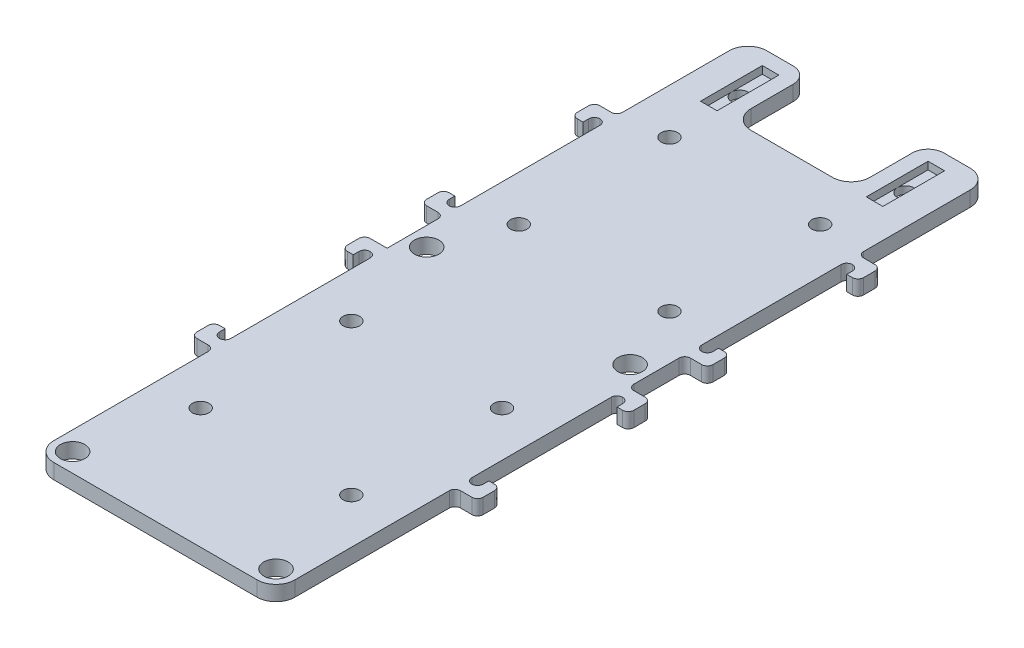
SolidWorks part; units mm, degrees
ref_plane "Front Plane" through (0, 0, 0) normal (0, 0, 1) x (1, 0, 0)
ref_plane "Top Plane" through (0, 0, 0) normal (0, 1, 0) x (1, 0, 0)
ref_plane "Right Plane" through (0, 0, 0) normal (1, 0, 0) x (0, 0, -1)
sketch "Sketch1" plane through (0, 0, 0) normal (0, 1, 0) x (1, 0, 0)
  line L0 (0, 42.225) -> (0, -42.225) construction
  line L1 (16, 42.225) -> (-16, 42.225)
  line L2 (16, 42.225) -> (16, -42.225)
  line L3 (16, -42.225) -> (-16, -42.225)
  line L4 (-16, 42.225) -> (-16, -42.225)
  line L5 (16, 42.225) -> (-16, -42.225) construction
  line L6 (16, -42.225) -> (-16, 42.225) construction
  line L12 (-12.1, 50.425) -> (-12.1, 52.425) construction
  line L17 (-11, 52.425) -> (-11, 42.225) construction
  line L18 (-7.9, 42.225) -> (-14.1, 42.225)
  line L20 (-10, 36) -> (10, 36)
  line L21 (-10, 36) -> (-10, 16)
  line L22 (-10, 16) -> (10, 16)
  line L23 (10, 36) -> (10, 16)
  line L24 (-10, 36) -> (10, 16) construction
  line L25 (-10, 16) -> (10, 36) construction
  line L26 (-14.5, 10.775) -> (14.5, 10.775)
  line L27 (-14.5, 10.775) -> (-14.5, 41.225)
  line L28 (-14.5, 41.225) -> (14.5, 41.225)
  line L29 (14.5, 10.775) -> (14.5, 41.225)
  line L30 (-14.5, 10.775) -> (14.5, 41.225) construction
  line L31 (-14.5, 41.225) -> (14.5, 10.775) construction
  line L32 (-10, -6.225) -> (10, -6.225)
  line L33 (-10, -6.225) -> (-10, -26.225)
  line L34 (-10, -26.225) -> (10, -26.225)
  line L35 (10, -6.225) -> (10, -26.225)
  line L36 (-10, -6.225) -> (10, -26.225) construction
  line L37 (-10, -26.225) -> (10, -6.225) construction
  line L38 (-15.75, -36.225) -> (15.75, -36.225)
  line L39 (-15.75, -36.225) -> (-15.75, 3.775)
  line L40 (-15.75, 3.775) -> (15.75, 3.775)
  line L41 (15.75, -36.225) -> (15.75, 3.775)
  line L42 (-15.75, -36.225) -> (15.75, 3.775) construction
  line L43 (-15.75, 3.775) -> (15.75, -36.225) construction
  line L48 (-7.9, 42.225) -> (-7.9, 52.425)
  line L49 (-7.9, 52.425) -> (-14.1, 52.425)
  line L59 (-14.1, 42.225) -> (-14.1, 52.425)
  line L63 (-12.1, 50.425) -> (-9.9, 50.425)
  line L64 (-12.1, 50.425) -> (-12.1, 42.225)
  line L65 (-12.1, 42.225) -> (-9.9, 42.225)
  line L66 (-9.9, 50.425) -> (-9.9, 42.225)
  line L67 (-12.1, 50.425) -> (-9.9, 42.225) construction
  line L68 (-12.1, 42.225) -> (-9.9, 50.425) construction
  line L69 (-12.1, 50.425) -> (-14.1, 50.425) construction
  line L74 (7.9, 42.225) -> (14.1, 42.225)
  line L75 (14.1, 42.225) -> (14.1, 52.425)
  line L76 (7.9, 52.425) -> (14.1, 52.425)
  line L77 (7.9, 42.225) -> (7.9, 52.425)
  line L78 (12.1, 50.425) -> (9.9, 50.425)
  line L79 (12.1, 50.425) -> (12.1, 42.225)
  line L80 (12.1, 42.225) -> (9.9, 42.225)
  line L81 (9.9, 50.425) -> (9.9, 42.225)
  line L82 (-14.5, 10.775) -> (-14.5, 3.775) construction
  line L83 (-14.5, 7.275) -> (16, 7.275) construction
  line L89 (-13.5, -37.225) -> (-16, -37.225) construction
  line L94 (-14.1, 52.425) -> (-16, 52.425)
  line L95 (-14.1, 52.425) -> (-14.1, 42.225)
  line L96 (-14.1, 42.225) -> (-16, 42.225)
  line L97 (-16, 52.425) -> (-16, 42.225)
  line L98 (14.1, 52.425) -> (16, 52.425)
  line L99 (14.1, 52.425) -> (14.1, 42.225)
  line L100 (14.1, 42.225) -> (16, 42.225)
  line L101 (16, 52.425) -> (16, 42.225)
  circle A3 centre (-10, 36) radius 1.1
  circle A4 centre (10, 36) radius 1.1
  circle A5 centre (10, 16) radius 1.1
  circle A6 centre (-10, 16) radius 1.1
  circle A7 centre (-10, -6.225) radius 1.1
  circle A8 centre (10, -6.225) radius 1.1
  circle A9 centre (10, -26.225) radius 1.1
  circle A10 centre (-10, -26.225) radius 1.1
  circle A37 centre (-13.5, 7.275) radius 2.5
  circle A38 centre (-13.5, 7.275) radius 1.625
  circle A39 centre (13.5, 7.275) radius 1.625
  circle A40 centre (-13.5, -39.725) radius 2.5
  circle A41 centre (-13.5, -39.725) radius 1.625
  circle A42 centre (13.5, -39.725) radius 1.625
  point P0 (0, 0)
  point P8 (0, 0)
  point P16 (0, 26)
  point P26 (0, 26)
  point P31 (0, -16.225)
  point P36 (0, -16.225)
  point P61 (-11, 46.325)
  dimension "D3" = 2
  dimension "D17" = 2.2
  dimension "D22" = 5
  dimension "D23" = 3.25
  dimension "D8" = 32
  dimension "D9" = 22
  dimension "D10" = 20
  dimension "D11" = 29
  dimension "D12" = 30.45
  dimension "D13" = 40
  dimension "D14" = 31.5
  dimension "D15" = 1
  dimension "D16" = 7
  dimension "D18" = 2.2
  dimension "D20" = 8.2
  dimension "D24" = 1
extrude "Base shape" add sketch "Sketch1" along normal blind 2 contours L63 L66 L1 L48 L49 L59 L18 L64 | L81 L78 L79 L1 L75 L76 L77 | L94 L97 L1 L59 | L101 L98 L75 L1 | L1 L4 L3 L2 | A4 | A3 | A7 | A8 | A9 | A10 | A5 | A6 | A39 | A38 | A41 | A42 region at (15.05, 0, -47.325) region at (13.1, 0, -42.3444) region at (-8.9, 0, -42.3444) region at (-15.05, 0, -47.325)
sketch "Sketch2" plane through (0, 0, 0) normal (0, -1, 0) x (1, 0, 0)
  line L0 (-12.1, -42.225) -> (-9.9, -50.425) construction
  line L1 (12.1, -42.225) -> (9.9, -50.425) construction
  line L4 (12.1, -42.225) -> (9.9, -42.225)
  line L5 (12.1, -50.425) -> (12.1, -42.225)
  line L6 (9.9, -50.425) -> (12.1, -50.425)
  line L7 (9.9, -42.225) -> (9.9, -50.425)
  line L8 (12.1, -42.225) -> (9.9, -42.225)
  line L9 (12.1, -50.425) -> (12.1, -42.225)
  line L10 (9.9, -50.425) -> (12.1, -50.425)
  line L11 (9.9, -42.225) -> (9.9, -50.425)
  line L12 (-9.9, -42.225) -> (-12.1, -42.225)
  line L13 (-9.9, -50.425) -> (-9.9, -42.225)
  line L14 (-12.1, -50.425) -> (-9.9, -50.425)
  line L15 (-12.1, -42.225) -> (-12.1, -50.425)
  line L16 (-9.9, -42.225) -> (-12.1, -42.225)
  line L17 (-9.9, -50.425) -> (-9.9, -42.225)
  line L18 (-12.1, -50.425) -> (-9.9, -50.425)
  line L19 (-12.1, -42.225) -> (-12.1, -50.425)
  circle A0 centre (-11, -46.325) radius 1.1
  circle A1 centre (11, -46.325) radius 1.1
  dimension "D1" = 0
  dimension "D2" = 0
extrude "Camera mount pockets" add sketch "Sketch2" against normal offset from surface (1 mm away) 1 contours A0 L19 | A0 L17 | A1 L9 | A1 L11 region at (11, 0, -43.8523) region at (11, 0, -48.7977) region at (-11, 0, -43.8523) region at (-11, 0, -48.7977) up to face at (11, 2, -46.325)
fillet "Main fillets" radius 2.5 6 edges at (7.9, 1, -42.225) (-7.9, 1, -42.225) (-16, 1, -52.425) (16, 1, -52.425) (-16, 1, 42.225) (16, 1, 42.225)
fillet "Inner camera fillets" radius 2.1 2 edges at (-7.9, 1, -52.425) (7.9, 1, -52.425)
sketch "Sketch3" [suppressed] plane through (0, 2, 0) normal (0, 1, 0) x (1, 0, 0)
  line L6 (12.1, 42.225) -> (12.1, 50.425)
  line L7 (9.9, 42.225) -> (12.1, 42.225)
  line L8 (-10, 52.425) -> (-13.5, 52.425)
  line L9 (-16, 49.925) -> (-16, -39.725)
  line L10 (-13.5, -42.225) -> (13.5, -42.225)
  line L11 (16, -39.725) -> (16, 49.925)
  line L12 (13.5, 52.425) -> (10, 52.425)
  line L13 (7.9, 50.325) -> (7.9, 44.725)
  line L14 (5.4, 42.225) -> (-5.4, 42.225)
  line L15 (-7.9, 44.725) -> (-7.9, 50.325)
  line L16 (-10, 52.425) -> (-13.5, 52.425)
  line L17 (-16, 49.925) -> (-16, -39.725)
  line L18 (-13.5, -42.225) -> (13.5, -42.225)
  line L19 (16, -39.725) -> (16, 49.925)
  line L20 (13.5, 52.425) -> (10, 52.425)
  line L21 (7.9, 50.325) -> (7.9, 44.725)
  line L22 (5.4, 42.225) -> (-5.4, 42.225)
  line L23 (-7.9, 44.725) -> (-7.9, 50.325)
  line L24 (9.9, 50.425) -> (9.9, 42.225)
  line L25 (12.1, 50.425) -> (9.9, 50.425)
  line L26 (12.1, 42.225) -> (12.1, 50.425)
  line L27 (9.9, 42.225) -> (12.1, 42.225)
  line L28 (9.9, 50.425) -> (9.9, 42.225)
  line L29 (12.1, 50.425) -> (9.9, 50.425)
  line L30 (-9.9, 42.225) -> (-9.9, 50.425)
  line L31 (-12.1, 42.225) -> (-9.9, 42.225)
  line L32 (-12.1, 50.425) -> (-12.1, 42.225)
  line L33 (-9.9, 50.425) -> (-12.1, 50.425)
  line L34 (-9.9, 42.225) -> (-9.9, 50.425)
  line L35 (-12.1, 42.225) -> (-9.9, 42.225)
  line L36 (-12.1, 50.425) -> (-12.1, 42.225)
  line L37 (-9.9, 50.425) -> (-12.1, 50.425)
  circle A0 centre (13.5, -39.725) radius 1.625 construction
  circle A1 centre (-13.5, -39.725) radius 1.625 construction
  circle A2 centre (-13.5, 7.275) radius 1.625 construction
  circle A3 centre (-10, -6.225) radius 1.1 construction
  circle A4 centre (-10, -26.225) radius 1.1 construction
  circle A5 centre (10, -26.225) radius 1.1 construction
  circle A6 centre (10, -6.225) radius 1.1 construction
  circle A7 centre (13.5, 7.275) radius 1.625 construction
  arc A8 (-13.5, 52.425) -> (-16, 49.925) centre (-13.5, 49.925) ccw
  arc A9 (-16, -39.725) -> (-13.5, -42.225) centre (-13.5, -39.725) ccw
  arc A10 (13.5, -42.225) -> (16, -39.725) centre (13.5, -39.725) ccw
  arc A11 (16, 49.925) -> (13.5, 52.425) centre (13.5, 49.925) ccw
  arc A12 (-7.9, 50.325) -> (-10, 52.425) centre (-10, 50.325) ccw
  arc A13 (5.4, 42.225) -> (7.9, 44.725) centre (5.4, 44.725) ccw
  arc A14 (-7.9, 44.725) -> (-5.4, 42.225) centre (-5.4, 44.725) ccw
  arc A15 (-7.9, 50.325) -> (-10, 52.425) centre (-10, 50.325) ccw
  arc A16 (-13.5, 52.425) -> (-16, 49.925) centre (-13.5, 49.925) ccw
  arc A17 (-16, -39.725) -> (-13.5, -42.225) centre (-13.5, -39.725) ccw
  arc A18 (13.5, -42.225) -> (16, -39.725) centre (13.5, -39.725) ccw
  arc A19 (16, 49.925) -> (13.5, 52.425) centre (13.5, 49.925) ccw
  arc A21 (5.4, 42.225) -> (7.9, 44.725) centre (5.4, 44.725) ccw
  arc A22 (-7.9, 44.725) -> (-5.4, 42.225) centre (-5.4, 44.725) ccw
  circle A24 centre (-10, 16) radius 1.1 construction
  circle A25 centre (-10, 36) radius 1.1 construction
  circle A26 centre (10, 36) radius 1.1 construction
  circle A27 centre (10, 16) radius 1.1 construction
  circle A28 centre (10, 16) radius 1.1
  circle A29 centre (10, 36) radius 1.1
  circle A30 centre (-10, 36) radius 1.1
  circle A31 centre (-10, 16) radius 1.1
  circle A32 centre (13.5, 7.275) radius 1.625
  circle A33 centre (10, -6.225) radius 1.1
  circle A34 centre (10, -26.225) radius 1.1
  circle A35 centre (-10, -26.225) radius 1.1
  circle A36 centre (-10, -6.225) radius 1.1
  circle A37 centre (13.5, -39.725) radius 1.625
  circle A38 centre (-13.5, -39.725) radius 1.625
  circle A39 centre (-13.5, 7.275) radius 1.625
  arc A48 (10, 52.425) -> (7.9, 50.325) centre (10, 50.325) ccw
  arc A49 (10, 52.425) -> (7.9, 50.325) centre (10, 50.325) ccw
  dimension "D1" = 0
  dimension "D2" = 0
  dimension "D3" = 0
extrude "Boss-Extrude3" [suppressed] add sketch "Sketch3" along normal blind 1
sketch "Sketch4" [suppressed] plane through (0, 0, 0) normal (0, -1, 0) x (1, 0, 0)
  line L0 (0, 13.9568) -> (0, -8.6953) construction
  line L1 (-14.1, -38.5) -> (-5.9, -38.5)
  line L2 (-14.1, -38.5) -> (-14.1, -41.7)
  line L3 (-14.1, -41.7) -> (-5.9, -41.7)
  line L4 (-5.9, -38.5) -> (-5.9, -41.7)
  line L5 (-10, -38.5) -> (-10, -41.7) construction
  line L7 (14.1, -38.5) -> (5.9, -38.5)
  line L8 (14.1, -38.5) -> (14.1, -41.7)
  line L9 (14.1, -41.7) -> (5.9, -41.7)
  line L10 (5.9, -38.5) -> (5.9, -41.7)
  line L11 (-14.1, -38.5) -> (-10.9, -41.7) construction
  line L12 (-14.1, -40.1) -> (-5.9, -40.1) construction
  circle A0 centre (-10, -36) radius 2
  circle A1 centre (-13.3929, -39.2071) radius 1
  circle A2 centre (-13.3929, -40.9929) radius 1
  circle A3 centre (-6.6071, -39.2071) radius 1
  circle A4 centre (-6.6071, -40.9929) radius 1
  circle A5 centre (6.6071, -40.9929) radius 1
  circle A6 centre (6.6071, -39.2071) radius 1
  circle A7 centre (13.3929, -39.2071) radius 1
  circle A8 centre (13.3929, -40.9929) radius 1
  point P9 (-10, -38)
  dimension "D5" = 4
  dimension "D7" = 2
  dimension "D1" = 8.2
  dimension "D2" = 3.2
  dimension "D3" = 10
  dimension "D4" = 0.5
  dimension "D6" = 45
extrude "Cut-Extrude1" [suppressed] cut sketch "Sketch4" against normal offset from surface (2 mm away) 1 contours A2 L2 | A2 L3 | L2 A1 | L1 A1 | A3 L4 | A3 L1 | L4 A4 | L3 A4 | A5 L9 | A5 L10 | L10 A6 | L7 A6 | A7 L7 | A7 L8 | L8 A8 | L9 A8 | L3 L4 L1 L2 | L9 L10 L7 L8 up to face at (11, 0, -47.425)
sketch "Sketch5" [suppressed] plane through (0, 2, 0) normal (0, -1, 0) x (1, 0, 0)
  line L0 (-10, -38.5) -> (-10, -41.7) construction
  line L1 (-12.6858, -38.5) -> (-7.3142, -38.5) construction
  line L2 (-12.6858, -41.7) -> (-7.3142, -41.7) construction
  line L3 (0, 5.9884) -> (0, -5.6723) construction
  circle A0 centre (-10, -40.1) radius 1.1
  circle A1 centre (10, -40.1) radius 1.1
  dimension "D1" = 2.2
extrude "Cut-Extrude2" [suppressed] cut sketch "Sketch5" against normal up to next
sketch "Sketch6" plane through (0, 0, 0) normal (0, -1, 0) x (1, 0, 0)
  line L0 (0, -5.1) -> (0, 9.653) construction
  line L1 (13.5, 42.225) -> (-13.5, 42.225) construction
  line L2 (-15.5, -38.775) -> (15.5, -38.775)
  line L3 (-15.5, -38.775) -> (-15.5, 22.225)
  line L4 (-15.5, 22.225) -> (15.5, 22.225)
  line L5 (15.5, -38.775) -> (15.5, 22.225)
  line L6 (-15.5, -38.775) -> (15.5, 22.225) construction
  line L7 (-15.5, 22.225) -> (15.5, -38.775) construction
  line L8 (-15.5, -8.275) -> (15.5, -8.275) construction
  line L9 (-15.5, -8.275) -> (15.5, -38.775) construction
  line L10 (-16, -23.525) -> (16, -23.525) construction
  line L11 (-16, -49.925) -> (-16, 39.725) construction
  line L12 (16, -49.925) -> (16, 39.725) construction
  line L13 (17.5, -32.025) -> (19, -32.025)
  line L14 (16, -35.025) -> (19, -35.025)
  line L15 (16, -35.025) -> (16, -12.025)
  line L16 (16, -12.025) -> (19, -12.025)
  line L17 (19, -35.025) -> (19, -12.025)
  line L18 (16, -35.025) -> (19, -12.025) construction
  line L19 (16, -12.025) -> (19, -35.025) construction
  line L20 (16, -33.525) -> (17.5, -33.525)
  line L21 (16, -33.525) -> (16, -13.525)
  line L22 (16, -13.525) -> (17.5, -13.525)
  line L23 (17.5, -33.525) -> (17.5, -13.525)
  line L24 (16, -33.525) -> (17.5, -13.525) construction
  line L25 (16, -13.525) -> (17.5, -33.525) construction
  line L26 (17.5, -15.025) -> (19, -15.025)
  line L27 (-17.5, -32.025) -> (-19, -32.025)
  line L28 (-17.5, -15.025) -> (-19, -15.025)
  line L29 (-16, -33.525) -> (-16, -13.525)
  line L30 (-16, -33.525) -> (-17.5, -33.525)
  line L31 (-17.5, -33.525) -> (-17.5, -13.525)
  line L32 (-16, -13.525) -> (-17.5, -13.525)
  line L33 (-16, -35.025) -> (-16, -12.025)
  line L34 (-16, -35.025) -> (-19, -35.025)
  line L35 (-19, -35.025) -> (-19, -12.025)
  line L36 (-16, -12.025) -> (-19, -12.025)
  line L37 (16, 18.475) -> (19, 18.475)
  line L38 (16, 18.475) -> (16, -4.525)
  line L39 (16, -4.525) -> (19, -4.525)
  line L40 (19, 18.475) -> (19, -4.525)
  line L41 (16, 16.975) -> (17.5, 16.975)
  line L42 (16, 16.975) -> (16, -3.025)
  line L43 (16, -3.025) -> (17.5, -3.025)
  line L44 (17.5, 16.975) -> (17.5, -3.025)
  line L45 (17.5, -1.525) -> (19, -1.525)
  line L46 (17.5, 15.475) -> (19, 15.475)
  line L47 (-17.5, 15.475) -> (-19, 15.475)
  line L48 (-17.5, -1.525) -> (-19, -1.525)
  line L49 (-16, 16.975) -> (-16, -3.025)
  line L50 (-16, 16.975) -> (-17.5, 16.975)
  line L51 (-17.5, 16.975) -> (-17.5, -3.025)
  line L52 (-16, -3.025) -> (-17.5, -3.025)
  line L53 (-16, 18.475) -> (-16, -4.525)
  line L54 (-16, 18.475) -> (-19, 18.475)
  line L55 (-19, 18.475) -> (-19, -4.525)
  line L56 (-16, -4.525) -> (-19, -4.525)
  point P1 (0, -8.275)
  point P12 (0, -23.525)
  point P19 (17.5, -23.525)
  point P25 (16.75, -23.525)
  line M18 (16, -49.925) -> (16, 39.725)
  line M22 (-16, 39.725) -> (-16, -49.925)
  dimension "D1" = 61
  dimension "D2" = 31
  dimension "D3" = 20
  dimension "D4" = 23
  dimension "D5" = 3
  dimension "D6" = 1.5
  dimension "D7" = 20
  dimension "D8" = 1.5
extrude "Strap holders" add sketch "Sketch6" against normal up to surface (2 mm away) contours L23 L20 L14 L17 L13 M18 | L23 L26 L17 L16 L22 M18 | L45 L44 L43 L39 L40 M18 | L44 L46 L40 L37 L38 L41 | L54 L55 L47 L51 L50 M22 | L56 L52 L51 L48 L55 M22 | L36 L35 L28 L31 L32 M22 | L35 L34 L30 L31 L27 M22 region at (17.75, 0, -33.775) region at (17.75, 0, -3.275) region at (17.75, 0, -13.275) region at (17.75, 0, 17.225) region at (-17.75, 0, -33.775) region at (-17.75, 0, -3.275) region at (-17.75, 0, -13.275) region at (-17.75, 0, 17.225) up to face at (11, 2, -46.325)
fillet "Strap holder fillets" radius 0.75 39 edges at (19, 1, -35.025) (19, 1, -12.025) (-19, 1, 18.475) (-19, 1, -4.525) (-19, 1, -35.025) (-19, 1, -12.025) (-17.5, 1, -33.525) (-17.5, 1, -3.025) (-16, 1, -33.525) (-16, 1, -12.025) (-16, 1, -3.025) (-16, 1, 18.475) (-16, 1, 16.975) (-16, 1, -13.525) (-16, 1, -35.025) (16, 1, -3.025) (17.5, 1, -3.025) (17.5, 1, -13.525) (17.5, 1, -33.525) (16, 1, -33.525) (16, 1, -12.025) (16, 1, -35.025) (-17.5, 1, -13.525) (-17.5, 1, 16.975) (16, 1, -13.525) (16, 1, -4.525) (19, 1, -4.525) (17.5, 1, 16.975) (16, 1, 16.975) (19, 1, 18.475) (16, 1, 18.475) (-19, 1, -15.025) (-19, 1, -32.025) (-19, 1, -1.525) (-19, 1, 15.475) (19, 1, 15.475) (19, 1, -1.525) (19, 1, -15.025) (19, 1, -32.025)
